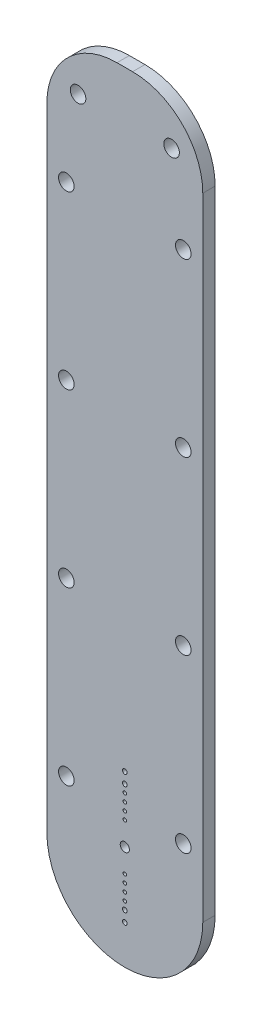
SolidWorks part; units mm, degrees
material "Acrylic (Medium-high impact)"
ref_plane "Front" through (0, 0, 0) normal (0, 0, 1) x (1, 0, 0)
ref_plane "Top" through (0, 0, 0) normal (0, 1, 0) x (1, 0, 0)
ref_plane "Right" through (0, 0, 0) normal (1, 0, 0) x (0, 0, -1)
sketch "Sketch2" plane through (0, 0, 0) normal (0, 0, 1) x (1, 0, 0)
  line L1 (-20, -100) -> (20, -100)
  line L2 (-20, -100) -> (-20, 100)
  line L3 (-20, 100) -> (20, 100)
  line L4 (20, -100) -> (20, 100)
  line L5 (-20, -100) -> (20, 100) construction
  line L6 (-20, 100) -> (20, -100) construction
  point P1 (0, 0)
  dimension "D1" = 200
  dimension "D2" = 40
extrude "Boss-Extrude1" add sketch "Sketch2" along normal blind 3.175
sketch "Sketch3" plane through (0, 0, 0) normal (0, 0, -1) x (-1, 0, 0)
  line L0 (20, -100) -> (-20, -100) construction
  line L1 (1.325, -88.5019) -> (-1.325, -88.5019)
  arc A0 (-1.325, -88.5019) -> (1.325, -88.5019) centre (0, -90) ccw
  dimension "D1" = 4
  dimension "D2" = 10
  dimension "D3" = 2.65
fillet "Fillet1" radius 20 2 edges at (20, -100, 1.5875) (-20, -100, 1.5875)
fillet "Fillet2" radius 18 2 edges at (20, 100, 1.5875) (-20, 100, 1.5875)
sketch "Sketch6" plane through (0, 0, 3.175) normal (0, 0, 1) x (1, 0, 0)
  line L0 (0, -113.8198) -> (0, 113.8198) construction
  line L1 (15, 67) -> (15, 23) construction
  line L2 (15, 23) -> (15, -21) construction
  line L3 (15, -21) -> (15, -65) construction
  line L4 (20, -80) -> (20, 82) construction
  line L5 (-15, -21) -> (-15, -65) construction
  line L6 (-15, 23) -> (-15, -21) construction
  line L7 (-15, 67) -> (-15, 23) construction
  circle A0 centre (15, 67) radius 2
  circle A1 centre (15, -21) radius 2
  circle A2 centre (15, 23) radius 2
  circle A3 centre (15, -65) radius 2
  circle A4 centre (-15, -65) radius 2
  circle A5 centre (-15, 23) radius 2
  circle A6 centre (-15, -21) radius 2
  circle A7 centre (-15, 67) radius 2
  point P11 (0, 0)
  dimension "D1" = 4
  dimension "D2" = 15
  dimension "5" = 5
  dimension "D3" = 15
extrude "Cut-Extrude4" cut sketch "Sketch6" against normal through all
sketch "Sketch7" plane through (0, 0, 3.175) normal (0, 0, 1) x (1, 0, 0)
  line L0 (-30.4029, 88) -> (30.4029, 88) construction
  circle A0 centre (-12, 88) radius 2
  circle A1 centre (12, 88) radius 2
  point P4 (0, 88)
  dimension "D1" = 4
  dimension "D2" = 4
  dimension "D3" = 12
  dimension "D4" = 12
extrude "Cut-Extrude5" cut sketch "Sketch7" against normal through all
sketch "Sketch8" plane through (0, 0, 3.175) normal (0, 0, 1) x (1, 0, 0)
  line L0 (0, -90) -> (0, -49.3452) construction
  circle A0 centre (0, -90) radius 0.6
  circle A1 centre (0, -87.25) radius 0.6
  circle A2 centre (0, -85.25) radius 0.45
  circle A3 centre (0, -83.25) radius 0.45
  circle A4 centre (0, -81.25) radius 0.45
  circle A5 centre (0, -79.25) radius 0.45
  circle A6 centre (0, -67.25) radius 0.45
  circle A7 centre (0, -65.25) radius 0.45
  circle A8 centre (0, -63.25) radius 0.45
  circle A9 centre (0, -61.25) radius 0.45
  circle A10 centre (0, -59.25) radius 0.6
  circle A11 centre (0, -56.5) radius 0.6
  circle A12 centre (0, -73.25) radius 1.175
  point P25 (0, 0)
  dimension "D1" = 1.2
  dimension "D2" = 0.9
  dimension "D14" = 2.35
  dimension "D3" = 2.75
  dimension "D4" = 2
  dimension "D5" = 2
  dimension "D6" = 2
  dimension "D7" = 2
  dimension "D8" = 2.75
  dimension "D9" = 2
  dimension "D10" = 2
  dimension "D11" = 2
  dimension "D12" = 2
  dimension "D13" = 12
  dimension "D15" = 6
extrude "Cut-Extrude6" cut sketch "Sketch8" against normal through all
